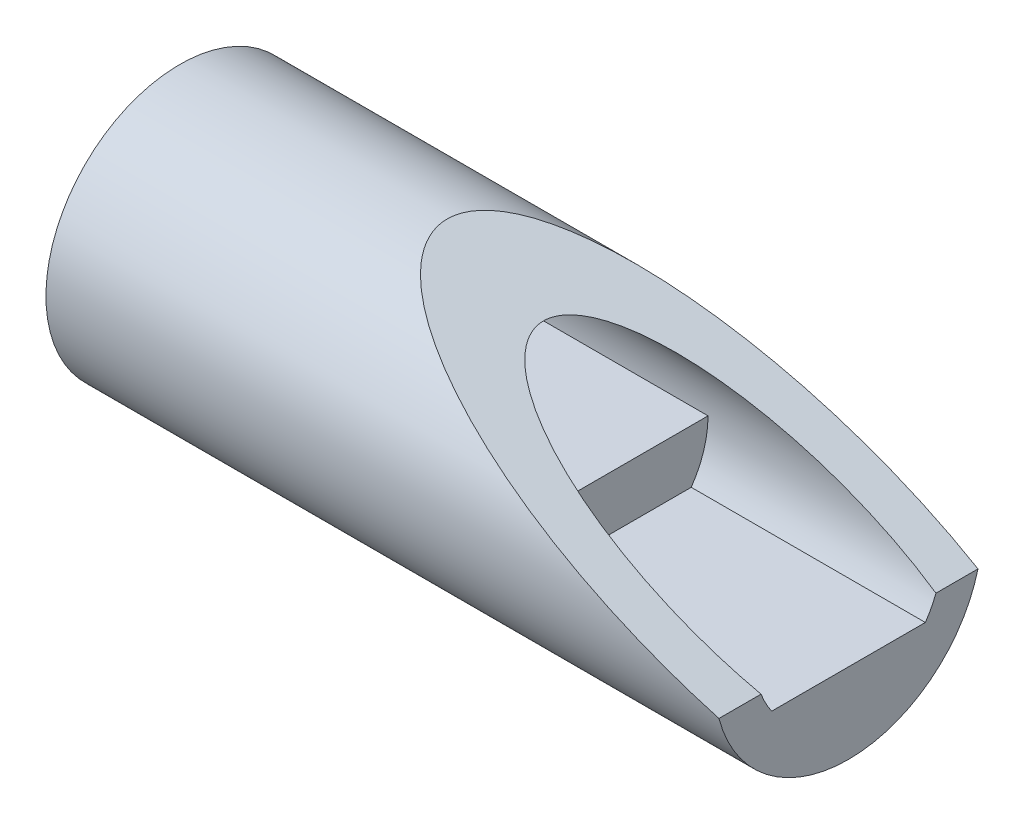
SolidWorks part; units mm, degrees
ref_plane "Front Plane" through (0, 0, 0) normal (0, 0, 1) x (1, 0, 0)
ref_plane "Top Plane" through (0, 0, 0) normal (0, 1, 0) x (1, 0, 0)
ref_plane "Right Plane" through (0, 0, 0) normal (1, 0, 0) x (0, 0, -1)
sketch "Sketch1" plane through (0, 0, 0) normal (1, 0, 0) x (0, 0, -1)
  line L0 (-14, 0) -> (14, 0)
  line L1 (-11.4891, -8) -> (11.4891, -8)
  circle A0 centre (0, 0) radius 20
  circle A1 centre (0, 0) radius 14
  point P8 (0, 0)
  point P9 (16, 0)
  dimension "D1" = 40
  dimension "D2" = 28
  dimension "D3" = 8
extrude "Boss-Extrude1" add sketch "Sketch1" along normal blind 65 contours L0 A1 L1 region at (0, -3.8758, 0)
extrude "Boss-Extrude2" add sketch "Sketch1<4>" along normal blind 100 contours L1 A1 | A0 A1 region at (0, -10.4504, 0) region at (0, 0, 19.4343)
sketch "Sketch1<4>" plane through (0, 0, 0) normal (1, 0, 0) x (0, 0, -1) same geometry as "Sketch1"
sketch "Sketch2" plane through (0, 0, 0) normal (0, 0, 1) x (1, 0, 0)
  line L0 (40, 20) -> (100, -5)
  line L1 (100, 20) -> (0, 20) construction
  line L2 (100, -20) -> (100, 20) construction
  line L3 (40, 20) -> (100, 20)
  line L4 (100, 20) -> (100, -5)
  dimension "D1" = 15
  dimension "D2" = 40
extrude "Cut-Extrude1" cut sketch "Sketch2" against normal up to next and the other way up to next
